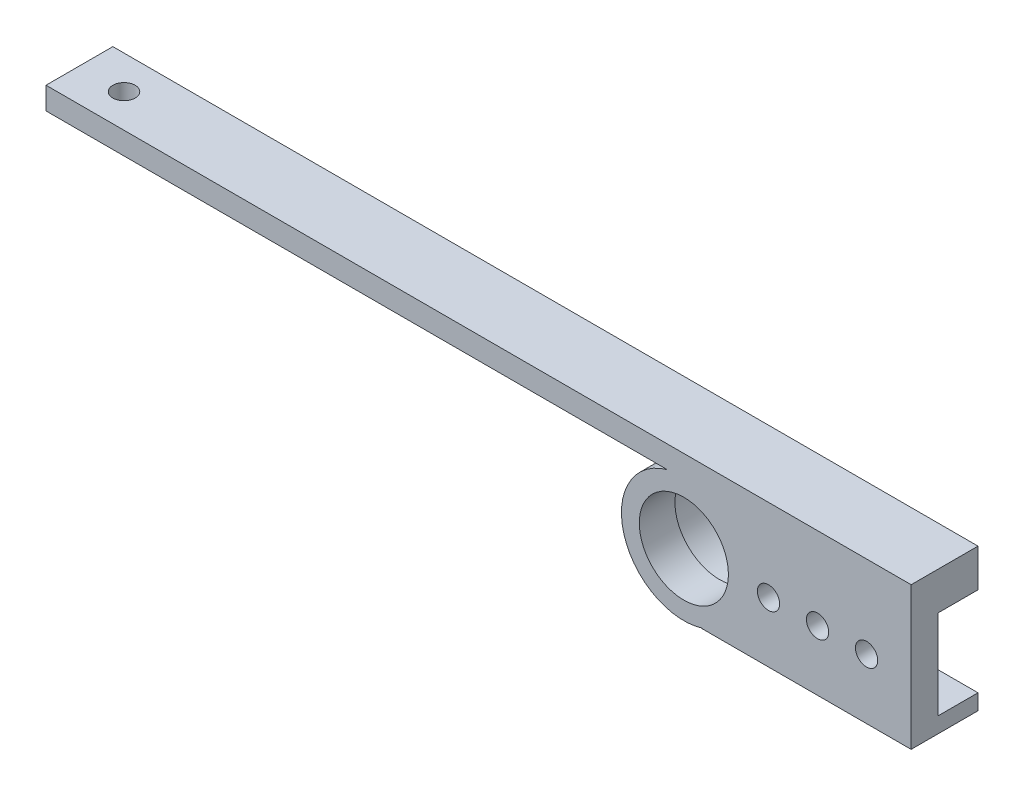
SolidWorks part; units mm, degrees
ref_plane "前视基准面" through (0, 0, 0) normal (0, 0, 1) x (1, 0, 0)
ref_plane "上视基准面" through (0, 0, 0) normal (0, 1, 0) x (1, 0, 0)
ref_plane "右视基准面" through (0, 0, 0) normal (1, 0, 0) x (0, 0, -1)
sketch "草图1" plane through (0, 0, 0) normal (0, 0, 1) x (1, 0, 0)
  line L1 (20, -10) -> (-20, -10)
  line L2 (20, -10) -> (20, 10)
  line L3 (20, 10) -> (-20, 10)
  line L4 (-20, -10) -> (-20, 10)
  line L5 (20, -10) -> (-20, 10) construction
  line L6 (20, 10) -> (-20, -10) construction
  point P0 (0, 0)
  dimension "D1" = 40
  dimension "D2" = 20
extrude "凸台-拉伸1" add sketch "草图1" along normal blind 6
sketch "草图2" plane through (0, 0, 6) normal (0, 0, 1) x (1, 0, 0)
  line L0 (20, -10) -> (20, 10) construction
  circle A0 centre (10, 0) radius 2.5
  circle A1 centre (-1, 0) radius 2.5
  circle A2 centre (-12, 0) radius 2.5
  dimension "D1" = 10
  dimension "D2" = 5
  dimension "D3" = 3
extrude "切除-拉伸1" cut sketch "草图2" against normal through all
sketch "草图3" plane through (0, 0, 6) normal (0, 0, 1) x (1, 0, 0)
  line L0 (20, 13.5) -> (20, 10)
  line L1 (20, -13.5) -> (-26.894, -13.5)
  line L3 (20, 13.5) -> (-26.894, 13.5)
  line L4 (-20, 10) -> (-20, -10)
  line L5 (-20, -10) -> (20, -10)
  line L6 (20, -10) -> (20, 10)
  line L7 (20, 10) -> (-20, 10)
  line L8 (-20, 10) -> (-20, -10)
  line L9 (-20, -10) -> (20, -10)
  line L10 (20, -10) -> (20, 10)
  line L11 (20, 10) -> (-20, 10)
  line L12 (-26.894, -13.5) -> (-26.894, 13.5)
  line L13 (20, -10.0394) -> (-26.894, 13.5) construction
  line L14 (20, 10.0394) -> (-26.894, -13.5) construction
  line L15 (20, -10) -> (20, -13.5)
  circle A0 centre (-31, 0) radius 11
  circle A1 centre (-31, 0) radius 14
  point P2 (0, 0)
  line M10 (-20, 10) -> (-20, -10)
  line M11 (-20, -10) -> (20, -10)
  line M13 (20, 10) -> (-20, 10)
  dimension "D3" = 22
  dimension "D4" = 28
  dimension "D2" = 3.5
  dimension "D1" = 0
extrude "凸台-拉伸2" add sketch "草图3" against normal blind 15 contours L3 A1 L1 L12 A0 | A1 L1 L15 M11 M10 | L1 A1 L8 A0 L12 | L8 A1 L3 L12 A0 | L8 A1 | A1 L0 L3 M10 M13 region at (-1.9449, 11.7771, 6) region at (-1.9449, -11.7771, 6) region at (-23.0173, 9.0328, 6) region at (-27.2274, 11.7946, 6) region at (-18.7882, 0, 6) region at (-23.0173, -9.0328, 6)
sketch "草图5" plane through (0, 0, 6) normal (0, 0, 1) x (1, 0, 0)
  circle A0 centre (-31, 0) radius 10
  circle A1 centre (-31, 0) radius 11 construction
  circle A2 centre (-31, 0) radius 11
  dimension "D1" = 20
extrude "凸台-拉伸3" add sketch "草图5" against normal blind 8
sketch "草图6" plane through (0, 0, 6) normal (0, 0, 1) x (1, 0, 0)
  circle A0 centre (-31, 0) radius 8.5
  circle A1 centre (-31, 0) radius 10 construction
  circle A2 centre (-31, 0) radius 10
  dimension "D1" = 17
sketch "草图7" plane through (0, 13.5, 0) normal (0, 1, 0) x (1, 0, 0)
  circle A0 centre (-16.8213, 3.0525) radius 3.3366
sketch "草图8" plane through (20, 0, 0) normal (1, 0, 0) x (0, 0, -1)
  line L1 (-6, 13.5) -> (9, 13.5)
  line L2 (-6, 13.5) -> (-6, 18.5)
  line L3 (-6, 18.5) -> (9, 18.5)
  line L4 (9, 13.5) -> (9, 18.5)
  dimension "D1" = 5
extrude "凸台-拉伸4" add sketch "草图8" against normal blind 200
sketch "草图9" plane through (0, 0, 6) normal (0, 0, 1) x (1, 0, 0)
  line L1 (-29.5663, 15.6648) -> (-25.1627, 15.6648)
  line L2 (-29.5663, 15.6648) -> (-29.5663, 11.9284)
  line L3 (-29.5663, 11.9284) -> (-25.1627, 11.9284)
  line L4 (-25.1627, 15.6648) -> (-25.1627, 11.9284)
extrude "凸台-拉伸5" add sketch "草图9" against normal through all
sketch "草图11" plane through (0, 18.5, 0) normal (0, 1, 0) x (1, 0, 0)
  line L0 (-118.4338, -6) -> (-118.4338, 9)
  line L1 (-180, -6) -> (20, -6) construction
  line L2 (-118.4338, 246.7017) -> (-118.4338, -123.2983) construction
  line L3 (-180, 9) -> (20, 9) construction
sketch "草图13" plane through (0, 18.5, 0) normal (0, 1, 0) x (1, 0, 0)
  line L1 (-118.4338, -6) -> (-183.1111, -6)
  line L2 (-118.4338, -6) -> (-118.4338, 12.5245)
  line L3 (-118.4338, 12.5245) -> (-183.1111, 12.5245)
  line L4 (-183.1111, -6) -> (-183.1111, 12.5245)
extrude "切除-拉伸2" cut sketch "草图13" against normal through all
sketch "草图14" plane through (0, 18.5, 0) normal (0, 1, 0) x (1, 0, 0)
  line L0 (-174.1103, 11.0465) -> (-174.1103, -39.4434)
  line L1 (-174.1103, 215.8314) -> (-174.1103, -154.1686) construction
sketch "草图15" plane through (0, 18.5, 0) normal (0, 1, 0) x (1, 0, 0)
  line L0 (-174.1103, 11.0465) -> (-174.1103, -39.4434) construction
  line L1 (-118.4338, -6) -> (-174.1103, -6)
  line L2 (-118.4338, -6) -> (-118.4338, 9)
  line L3 (-118.4338, 9) -> (-174.1103, 9)
  line L4 (-174.1103, -6) -> (-174.1103, 9)
extrude "凸台-拉伸6" add sketch "草图15" against normal blind 5
sketch "草图16" plane through (0, 18.5, 0) normal (0, 1, 0) x (1, 0, 0)
  line L0 (-174.1103, 9) -> (-174.1103, -6)
  line L1 (-174.1103, 1.5) -> (-164.1103, 1.5) construction
  circle A0 centre (-164.1103, 1.5) radius 2.5
  dimension "D2" = 5
  dimension "D1" = 10
extrude "切除-拉伸3" cut sketch "草图16" against normal blind 10 contours A0 region at (-164.1103, 18.5, -1.5)
